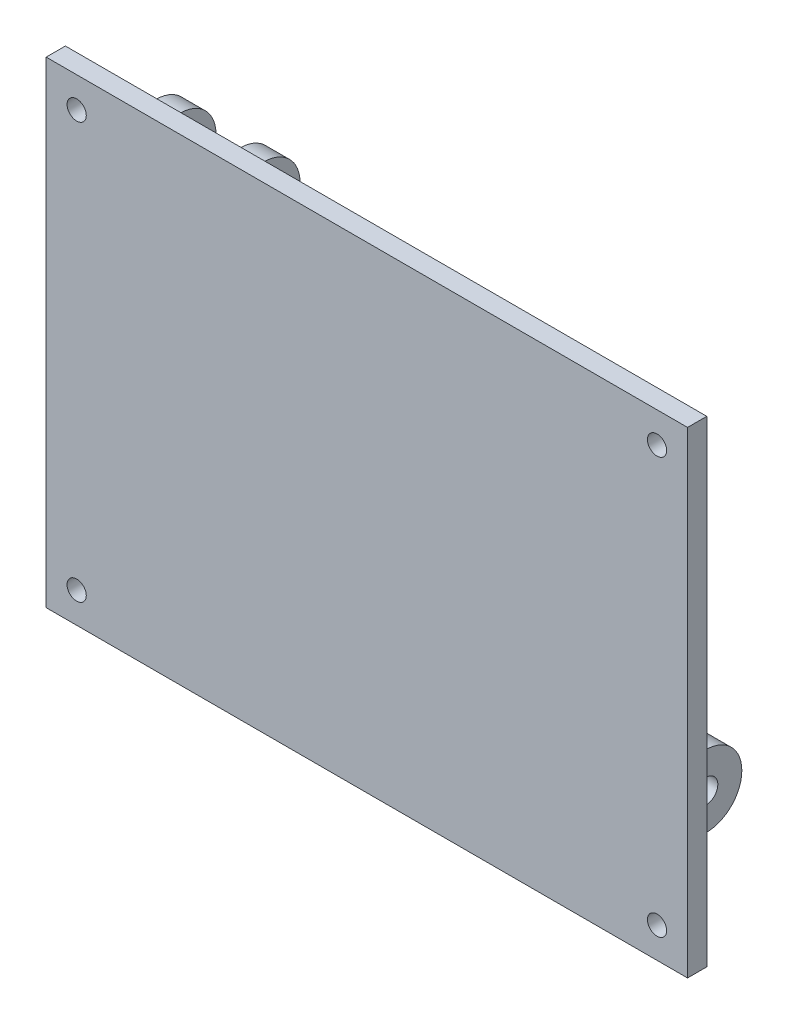
SolidWorks part; units mm, degrees
ref_plane "Front Plane" through (0, 0, 0) normal (0, 0, 1) x (1, 0, 0)
ref_plane "Top Plane" through (0, 0, 0) normal (0, 1, 0) x (1, 0, 0)
ref_plane "Right Plane" through (0, 0, 0) normal (1, 0, 0) x (0, 0, -1)
sketch "Sketch1" plane through (0, 0, 0) normal (0, 0, 1) x (1, 0, 0)
  line L2 (-114.3, 38.1) -> (-114.3, 25.4)
  line L3 (-114.3, -38.1) -> (114.3, -38.1)
  line L4 (114.3, 38.1) -> (114.3, -38.1)
  line L5 (-58.9, 15) -> (-48.9, 15)
  line L6 (-88.9, 15) -> (-78.9, 15)
  line L8 (-88.9, 15) -> (-88.9, -15)
  line L9 (-88.9, -15) -> (-78.9, -15)
  line L10 (-78.9, 15) -> (-78.9, -15)
  line L11 (-88.9, 15) -> (-78.9, -15) construction
  line L12 (-88.9, -15) -> (-78.9, 15) construction
  line L13 (-58.9, 15) -> (-58.9, -15)
  line L14 (-58.9, -15) -> (-48.9, -15)
  line L15 (-48.9, 15) -> (-48.9, -15)
  line L16 (-58.9, 15) -> (-48.9, -15) construction
  line L17 (-58.9, -15) -> (-48.9, 15) construction
  line L18 (0, 0) -> (0, -38.1) construction
  line L19 (58.9, -15) -> (48.9, 15) construction
  line L20 (58.9, 15) -> (48.9, -15) construction
  line L21 (88.9, -15) -> (78.9, 15) construction
  line L22 (88.9, 15) -> (78.9, -15) construction
  line L23 (48.9, 15) -> (48.9, -15)
  line L24 (58.9, -15) -> (48.9, -15)
  line L25 (58.9, 15) -> (58.9, -15)
  line L26 (78.9, 15) -> (78.9, -15)
  line L27 (88.9, -15) -> (78.9, -15)
  line L28 (88.9, 15) -> (88.9, -15)
  line L29 (88.9, 15) -> (78.9, 15)
  line L30 (58.9, 15) -> (48.9, 15)
  line L32 (-140, 135) -> (-130, 135)
  line L33 (-140, 135) -> (-140, 105)
  line L34 (-140, 105) -> (-130, 105)
  line L35 (-95, 135) -> (-95, 105)
  line L37 (-105, 120) -> (-95, 120) construction
  line L39 (-114.3, 38.1) -> (-114.3, 160.4)
  line L40 (-114.3, 160.4) -> (114.3, 160.4)
  line L41 (114.3, 38.1) -> (114.3, 160.4)
  line L42 (-140, 135) -> (-130, 135)
  line L43 (-140, 135) -> (-140, 105)
  line L44 (-140, 105) -> (-130, 105)
  line L45 (-130, 135) -> (-130, 105)
  line L46 (-95, 135) -> (-105, 135)
  line L47 (-95, 135) -> (-95, 105)
  line L48 (-95, 105) -> (-105, 105)
  line L49 (-105, 135) -> (-105, 105)
  line L53 (-105, 135) -> (-95, 135)
  line L54 (-105, 105) -> (-95, 105)
  line L55 (-114.3, 160.4) -> (-152.7, 160.4)
  line L56 (-114.3, 160.4) -> (-114.3, 25.4)
  line L57 (-114.3, -38.1) -> (-152.7, -38.1)
  line L58 (-152.7, 160.4) -> (-152.7, -38.1)
  circle A0 centre (-140, 147.7) radius 4
  circle A7 centre (101.6, 147.7) radius 4
  circle A8 centre (101.6, -25.4) radius 4
  circle A9 centre (-140, -25.4) radius 4
  point P0 (0, 0)
  point P16 (-83.9, 0)
  point P23 (-53.9, 0)
  point P36 (53.9, 0)
  point P37 (83.9, 0)
  dimension "D4" = 8
  dimension "D8" = 10
  dimension "D6" = 8
  dimension "D7" = 12.7
  dimension "D9" = 8
  dimension "D10" = 12.7
  dimension "D11" = 12.7
  dimension "D12" = 8
  dimension "D13" = 12.7
  dimension "D14" = 12.7
  dimension "D3" = 12.7
  dimension "D5" = 12.7
  dimension "D25" = 12.7
  dimension "D1" = 76.2
  dimension "D2" = 228.6
  dimension "D15" = 30
  dimension "D16" = 10
  dimension "D17" = 120
  dimension "D18" = 25.4
  dimension "D20" = 114.3
  dimension "D21" = 38.1
  dimension "D22" = 10
  dimension "D23" = 51.1
  dimension "D24" = 30
  dimension "D26" = 25.4
  dimension "D27" = 25
  dimension "D29" = 12.7
  dimension "D19" = 2
extrude "Boss-Extrude1" add sketch "Sketch1" along normal blind 8 contours L10 L6 L8 L9 | L15 L5 L13 L14 | L4 L2 L3 A9 A8 A7 A0 L30 L25 L24 L23 L29 L28 L27 L26 L6 L10 L9 L8 L5 L15 L14 L13 | L25 L30 L23 L24 | L28 L29 L26 L27 | L46 L49 L48 L35 | L45 L32 L33 L34 region at (-18.4953, 61.8965, 0) region at (-53.9, 0, 0) region at (-83.9, 0, 0) region at (53.9, 0, 0) region at (83.9, 0, 0) region at (-135, 120, 0) region at (-100, 120, 0)
extrude "Boss-Extrude2" add sketch "Sketch1<3>" against normal blind 40 contours L10 L6 L8 L9 | L15 L5 L13 L14 | L28 L29 L26 L27 | L25 L30 L23 L24 | L46 L49 L48 L35 | L45 L32 L33 L34 region at (-53.9, 0, 0) region at (-83.9, 0, 0) region at (53.9, 0, 0) region at (83.9, 0, 0) region at (-135, 120, 0) region at (-100, 120, 0)
sketch "Sketch1<3>" plane through (0, 0, 0) normal (0, 0, 1) x (1, 0, 0) same geometry as "Sketch1"
fillet "Fillet1" radius 3 12 edges at (-88.9, 0, 0) (-48.9, 0, 0) (88.9, 0, 0) (48.9, 0, 0) (83.9, 15, 0) (53.9, 15, 0) (-53.9, 15, 0) (-83.9, 15, 0) (-83.9, -15, 0) (-53.9, -15, 0) (53.9, -15, 0) (83.9, -15, 0)
sketch "Sketch2" plane through (-88.9, 0, 0) normal (-1, 0, 0) x (0, 0, 1)
  line L0 (0, 77.7) -> (0, -38.1) construction
  line L1 (0, 77.7) -> (0, -38.1)
  line L2 (-40, 135) -> (-40, 105) construction
  line L3 (-40, 135) -> (0, 135) construction
  line L4 (-40, -15) -> (-3, -15)
  line L5 (-3, -15) -> (-3, 15)
  line L6 (-3, 15) -> (-40, 15)
  line L7 (-40, 15) -> (-40, -15)
  line L8 (-40, -15) -> (-3, -15)
  line L9 (-3, -15) -> (-3, 15)
  line L10 (-3, 15) -> (-40, 15)
  line L11 (-40, 15) -> (-40, -15)
  circle A0 centre (-25, 0) radius 5
  circle A1 centre (-25, 120) radius 4
  dimension "D2" = 15
  dimension "D3" = 10
  dimension "D4" = 15
  dimension "D5" = 15
  dimension "D6" = 8
  dimension "D1" = 0
extrude "Cut-Extrude1" cut sketch "Sketch2" against normal through all both and the other way through all contours A0 | A1 region at (-88.9, 0, -25) region at (-88.9, 120, -25)
fillet "Fillet2" radius 15 8 edges at (53.9, 15, -40) (53.9, -15, -40) (83.9, 15, -40) (83.9, -15, -40) (-53.9, 15, -40) (-53.9, -15, -40) (-83.9, -15, -40) (-83.9, 15, -40)
fillet "Fillet3" radius 15 4 edges at (-135, 135, -40) (-135, 105, -40) (-100, 105, -40) (-100, 135, -40)
